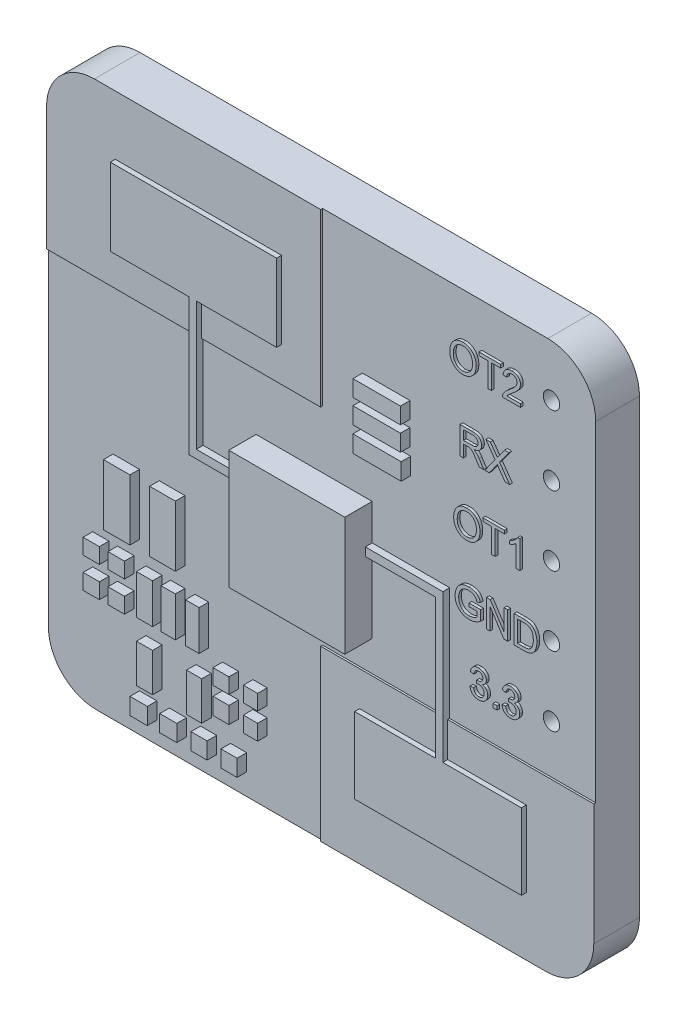
SolidWorks part; units mm, degrees
ref_plane "Plan de face" through (0, 0, 0) normal (0, 0, 1) x (1, 0, 0)
ref_plane "Plan de dessus" through (0, 0, 0) normal (0, 1, 0) x (1, 0, 0)
ref_plane "Plan de droite" through (0, 0, 0) normal (1, 0, 0) x (0, 0, -1)
sketch "pcb" plane through (0, 0, 0) normal (0, 0, 1) x (1, 0, 0)
  line L0 (-88.3794, 37.9422) -> (-68.3794, 37.9422) construction
  line L1 (-78.3986, 44.1613) -> (-91.3146, 44.1613) construction
  line L2 (-88.3829, 37.9329) -> (-88.3829, 45.4975)
  line L4 (-86.6329, 44.1613) -> (-70.1329, 44.1613)
  line L5 (-88.3829, 42.4113) -> (-88.3829, 25.9113)
  line L6 (-86.6329, 24.1613) -> (-70.1329, 24.1613)
  line L7 (-68.3829, 42.4113) -> (-68.3829, 25.9113)
  arc A0 (-70.1329, 44.1613) -> (-68.3829, 42.4113) centre (-70.1329, 42.4113) cw
  arc A1 (-86.6329, 44.1613) -> (-88.3829, 42.4113) centre (-86.6329, 42.4113) ccw
  arc A2 (-70.1329, 24.1613) -> (-68.3829, 25.9113) centre (-70.1329, 25.9113) ccw
  arc A3 (-88.3829, 25.9113) -> (-86.6329, 24.1613) centre (-86.6329, 25.9113) ccw
  circle A4 centre (-69.9993, 42.2724) radius 0.2996
  circle A5 centre (-69.9993, 39.7324) radius 0.2996
  circle A6 centre (-69.9993, 37.1924) radius 0.2996
  circle A7 centre (-69.9993, 34.6524) radius 0.2996
  circle A8 centre (-69.9993, 32.1124) radius 0.2996
  point P12 (-68.3829, 44.1613)
  point P15 (-88.3829, 44.1613)
  point P18 (-68.3829, 24.1613)
  point P21 (-88.3829, 24.1613)
  dimension "D4" = 1.75
  dimension "D1" = 20
  dimension "D2" = 20
  dimension "D3" = 20
  dimension "D5" = 5
sketch "composants" plane through (0, 0, 0) normal (0, 0, 1) x (1, 0, 0)
  line L0 (-82.7276, 39.1741) -> (-79.7936, 39.1741)
  line L1 (-85.8705, 41.9976) -> (-79.7936, 41.9976)
  line L2 (-85.8705, 41.9976) -> (-85.8705, 39.1741)
  line L3 (-85.8705, 39.1741) -> (-82.9897, 39.1741)
  line L4 (-79.7936, 41.9976) -> (-79.7936, 39.1741)
  line L5 (-76.9429, 29.0737) -> (-73.9791, 29.0737)
  line L6 (-76.9429, 29.0737) -> (-76.9429, 26.3015)
  line L7 (-76.9429, 26.3015) -> (-70.8492, 26.3015)
  line L8 (-70.8492, 29.0737) -> (-70.8492, 26.3015)
  line L10 (-73.9791, 29.0737) -> (-73.9791, 34.1766)
  line L11 (-73.9791, 34.4797) -> (-73.7211, 34.4797)
  line L12 (-73.7211, 29.0737) -> (-73.7211, 34.4797)
  line L13 (-73.7211, 34.4797) -> (-82.7276, 34.4797)
  line L14 (-73.7211, 34.4797) -> (-73.7211, 34.1766)
  line L15 (-73.9791, 34.1766) -> (-82.9897, 34.1766)
  line L16 (-82.9897, 34.4797) -> (-82.9897, 34.1766)
  line L17 (-82.9897, 34.1766) -> (-82.7276, 34.1766)
  line L18 (-82.9897, 34.1766) -> (-82.9897, 39.1741)
  line L20 (-82.7276, 34.4797) -> (-82.7276, 39.1741)
  line L21 (-73.7211, 29.0737) -> (-70.8492, 29.0737)
extrude "Boss.-Extru.1" add sketch "composants" along normal blind 0.25 contours L21 L12 L11 L13 L20 L0 L4 L1 L2 L3 L18 L16 L15 L10 L5 L6 L7 L8 region at (-78.3831, 34.1939, 0)
sketch "puce" plane through (0, 0, 0) normal (0, 0, 1) x (1, 0, 0)
  line L1 (-80.7922, 35.7946) -> (-76.5526, 35.7946)
  line L2 (-80.7922, 35.7946) -> (-80.7922, 31.4551)
  line L3 (-80.7922, 31.4551) -> (-76.5526, 31.4551)
  line L4 (-76.5526, 35.7946) -> (-76.5526, 31.4551)
extrude "Boss.-Extru.3" add sketch "puce" along normal blind 1
sketch "compos,ates" plane through (0, 0, 0) normal (0, 0, 1) x (1, 0, 0)
  line L1 (-86.0226, 32.558) -> (-85.0545, 32.558)
  line L2 (-86.0226, 32.558) -> (-86.0226, 30.3364)
  line L3 (-86.0226, 30.3364) -> (-85.0545, 30.3364)
  line L4 (-85.0545, 32.558) -> (-85.0545, 30.3364)
  line L5 (-84.3346, 32.558) -> (-83.3945, 32.558)
  line L6 (-84.3346, 32.558) -> (-84.3346, 30.3364)
  line L7 (-84.3346, 30.3364) -> (-83.3945, 30.3364)
  line L8 (-83.3945, 32.558) -> (-83.3945, 30.3364)
  line L9 (-86.7662, 29.7287) -> (-86.1717, 29.7287)
  line L10 (-86.7662, 29.7287) -> (-86.7662, 29.163)
  line L11 (-86.7662, 29.163) -> (-86.1717, 29.163)
  line L12 (-86.1717, 29.7287) -> (-86.1717, 29.163)
  line L13 (-85.8575, 29.7287) -> (-85.2525, 29.7287)
  line L14 (-85.8575, 29.7287) -> (-85.8575, 29.163)
  line L15 (-85.8575, 29.163) -> (-85.2525, 29.163)
  line L16 (-85.2525, 29.7287) -> (-85.2525, 29.163)
  line L17 (-86.7662, 28.6157) -> (-86.1717, 28.6157)
  line L18 (-86.7662, 28.6157) -> (-86.7662, 28.0473)
  line L19 (-86.7662, 28.0473) -> (-86.1717, 28.0473)
  line L20 (-86.1717, 28.6157) -> (-86.1717, 28.0473)
  line L21 (-85.8575, 28.6157) -> (-85.2525, 28.6157)
  line L22 (-85.8575, 28.6157) -> (-85.8575, 28.0473)
  line L23 (-85.8575, 28.0473) -> (-85.2525, 28.0473)
  line L24 (-85.2525, 28.6157) -> (-85.2525, 28.0473)
  line L25 (-82.0184, 27.9759) -> (-81.4369, 27.9759)
  line L26 (-82.0184, 27.9759) -> (-82.0184, 27.4147)
  line L27 (-82.0184, 27.4147) -> (-81.4369, 27.4147)
  line L28 (-81.4369, 27.9759) -> (-81.4369, 27.4147)
  line L29 (-80.9096, 27.9759) -> (-80.3889, 27.9759)
  line L30 (-80.9096, 27.9759) -> (-80.9096, 27.4147)
  line L31 (-80.9096, 27.4147) -> (-80.3889, 27.4147)
  line L32 (-80.3889, 27.9759) -> (-80.3889, 27.4147)
  line L33 (-82.0184, 27.0699) -> (-81.4369, 27.0699)
  line L34 (-82.0184, 27.0699) -> (-82.0184, 26.4614)
  line L35 (-82.0184, 26.4614) -> (-81.4369, 26.4614)
  line L36 (-81.4369, 27.0699) -> (-81.4369, 26.4614)
  line L37 (-80.9096, 27.0293) -> (-80.3889, 27.0293)
  line L38 (-80.9096, 27.0293) -> (-80.9096, 26.4614)
  line L39 (-80.9096, 26.4614) -> (-80.3889, 26.4614)
  line L40 (-80.3889, 27.0293) -> (-80.3889, 26.4614)
  line L41 (-85.0545, 25.5486) -> (-84.4186, 25.5486)
  line L42 (-85.0545, 25.5486) -> (-85.0545, 24.9401)
  line L43 (-85.0545, 24.9401) -> (-84.4186, 24.9401)
  line L44 (-84.4186, 25.5486) -> (-84.4186, 24.9401)
  line L45 (-83.9656, 25.5486) -> (-83.3436, 25.5486)
  line L46 (-83.9656, 25.5486) -> (-83.9656, 24.9401)
  line L47 (-83.9656, 24.9401) -> (-83.3436, 24.9401)
  line L48 (-83.3436, 25.5486) -> (-83.3436, 24.9401)
  line L49 (-82.823, 25.5486) -> (-82.2347, 25.5486)
  line L50 (-82.823, 25.5486) -> (-82.823, 24.9401)
  line L51 (-82.823, 24.9401) -> (-82.2347, 24.9401)
  line L52 (-82.2347, 25.5486) -> (-82.2347, 24.9401)
  line L53 (-81.7277, 25.5486) -> (-81.1394, 25.5486)
  line L54 (-81.7277, 25.5486) -> (-81.7277, 24.9401)
  line L55 (-81.7277, 24.9401) -> (-81.1394, 24.9401)
  line L56 (-81.1394, 25.5486) -> (-81.1394, 24.9401)
  line L57 (-84.8175, 27.4147) -> (-84.2293, 27.4147)
  line L58 (-84.8175, 27.4147) -> (-84.8175, 26.0084)
  line L59 (-84.8175, 26.0084) -> (-84.2293, 26.0084)
  line L60 (-84.2293, 27.4147) -> (-84.2293, 26.0084)
  line L61 (-82.9852, 27.4147) -> (-82.4308, 27.4147)
  line L62 (-82.9852, 27.4147) -> (-82.9852, 26.0084)
  line L63 (-82.9852, 26.0084) -> (-82.4308, 26.0084)
  line L64 (-82.4308, 27.4147) -> (-82.4308, 26.0084)
  line L65 (-84.8175, 29.6188) -> (-84.2293, 29.6188)
  line L66 (-84.8175, 29.6188) -> (-84.8175, 28.1652)
  line L67 (-84.8175, 28.1652) -> (-84.2293, 28.1652)
  line L68 (-84.2293, 29.6188) -> (-84.2293, 28.1652)
  line L69 (-83.9183, 29.6188) -> (-83.3945, 29.6188)
  line L70 (-83.9183, 29.6188) -> (-83.9183, 28.1652)
  line L71 (-83.9183, 28.1652) -> (-83.3945, 28.1652)
  line L72 (-83.3945, 29.6188) -> (-83.3945, 28.1652)
  line L73 (-83.0258, 29.6188) -> (-82.5289, 29.6188)
  line L74 (-83.0258, 29.6188) -> (-83.0258, 28.1652)
  line L75 (-83.0258, 28.1652) -> (-82.5289, 28.1652)
  line L76 (-82.5289, 29.6188) -> (-82.5289, 28.1652)
  line L77 (-76.9066, 39.6785) -> (-75.1684, 39.6785)
  line L78 (-76.9066, 39.6785) -> (-76.9066, 39.0829)
  line L79 (-76.9066, 39.0829) -> (-75.1684, 39.0829)
  line L80 (-75.1684, 39.6785) -> (-75.1684, 39.0829)
  line L81 (-76.9066, 38.8207) -> (-75.1684, 38.8207)
  line L82 (-76.9066, 38.8207) -> (-76.9066, 38.2154)
  line L83 (-76.9066, 38.2154) -> (-75.1684, 38.2154)
  line L84 (-75.1684, 38.8207) -> (-75.1684, 38.2154)
  line L85 (-76.9066, 37.9306) -> (-75.1425, 37.9306)
  line L86 (-76.9066, 37.9306) -> (-76.9066, 37.3123)
  line L87 (-76.9066, 37.3123) -> (-75.1425, 37.3123)
  line L88 (-75.1425, 37.9306) -> (-75.1425, 37.3123)
extrude "Boss.-Extru.4" add sketch "compos,ates" along normal blind 0.35 separate body
sketch "planmasse" plane through (0, 0, 0) normal (0, 0, 1) x (1, 0, 0)
  line L1 (-78.3642, 37.9073) -> (-88.3829, 37.9073)
  line L2 (-78.3642, 37.9073) -> (-78.3642, 44.1613)
  line L3 (-78.3642, 44.1613) -> (-86.6329, 44.1613)
  line L4 (-88.3829, 37.9073) -> (-88.3829, 42.4113)
  line L5 (-78.3642, 30.3412) -> (-68.3829, 30.3412)
  line L6 (-78.3642, 30.3412) -> (-78.3642, 24.1613)
  line L7 (-78.3642, 24.1613) -> (-70.1329, 24.1613)
  line L8 (-68.3829, 30.3412) -> (-68.3829, 25.9113)
  arc A0 (-86.6329, 44.1613) -> (-88.3829, 42.4113) centre (-86.6329, 42.4113) ccw
  arc A1 (-70.1329, 24.1613) -> (-68.3829, 25.9113) centre (-70.1329, 25.9113) ccw
  point P12 (-88.3829, 44.1613)
  point P15 (-68.3829, 24.1613)
  dimension "D1" = 1.75
extrude "Boss.-Extru.5" add sketch "planmasse" along normal blind 0.07
extrude "Boss.-Extru.6" add sketch "pcb" against normal blind 1.6 contours L5 A3 L6 A2 L7 A0 L4 A1 L2 A8 A7 A6 A5 A4 region at (-78.4127, 34.1506, 0)
sketch "Esquisse6" plane through (0, 0, 0) normal (0, 0, 1) x (1, 0, 0)
  text T0 "3.3" font "@Arial Unicode MS" height 1
  text T1 "GND" font "@Arial Unicode MS" height 1
  text T2 "OT1" font "@Arial Unicode MS" height 1
  text T3 "RX" font "@Arial Unicode MS" height 1
  text T4 "OT2" font "@Arial Unicode MS" height 1
extrude "Boss.-Extru.7" add sketch "Esquisse6" along normal blind 0.1
